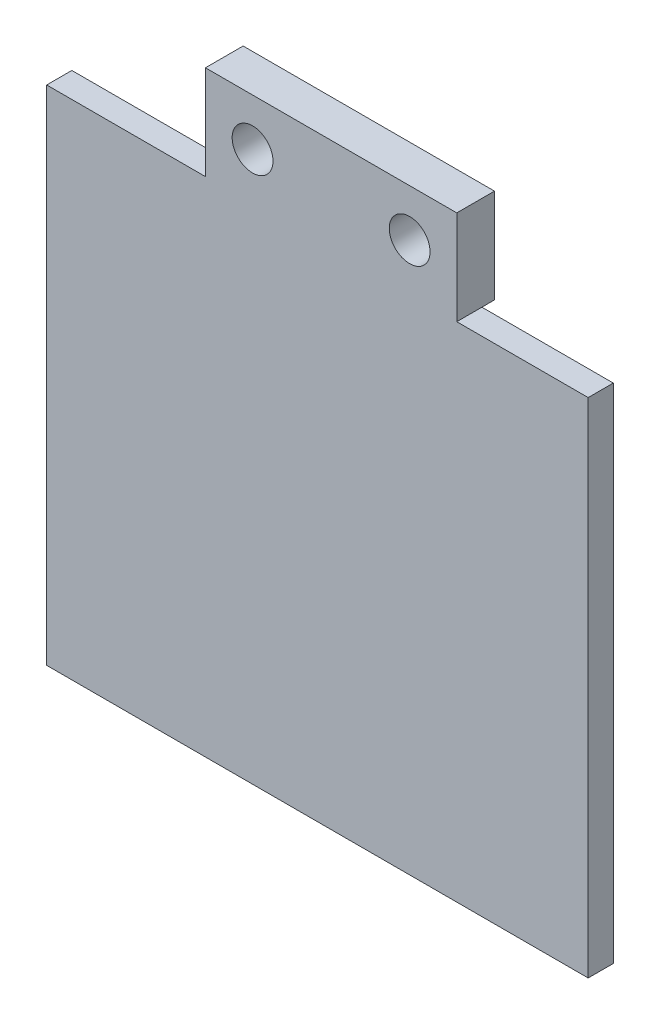
SolidWorks part; units mm, degrees
ref_plane "Front Plane" through (0, 0, 0) normal (0, 0, 1) x (1, 0, 0)
ref_plane "Top Plane" through (0, 0, 0) normal (0, 1, 0) x (1, 0, 0)
ref_plane "Right Plane" through (0, 0, 0) normal (1, 0, 0) x (0, 0, -1)
sketch "Sketch1" plane through (0, 0, 0) normal (0, 0, 1) x (1, 0, 0)
  line L0 (0, 0) -> (0, 40)
  line L1 (0, 40) -> (-7.5, 40)
  line L2 (-7.5, 40) -> (-7.5, 47.5)
  line L3 (-7.5, 47.5) -> (12.5, 47.5)
  line L4 (12.5, 47.5) -> (12.5, 40)
  line L5 (12.5, 40) -> (5, 40)
  line L6 (5, 40) -> (5, 0)
  line L7 (5, 0) -> (0, 0)
  circle A0 centre (-3.75, 43.75) radius 1.625
  circle A1 centre (8.75, 43.75) radius 1.625
  point P13 (12.5, 43.75)
  point P15 (-3.75, 40)
  point P17 (8.75, 40)
  dimension "D6" = 3.25
  dimension "D1" = 5
  dimension "D2" = 7.5
  dimension "D4" = 7.5
  dimension "D5" = 40
extrude "Boss-Extrude1" add sketch "Sketch1" along normal blind 3
sketch "Sketch2" plane through (0, 0, 3) normal (0, 0, -1) x (-1, 0, 0)
  line L1 (20.1317, 40) -> (-22.9556, 40)
  line L2 (20.1317, 40) -> (20.1317, 0)
  line L3 (20.1317, 0) -> (-22.9556, 0)
  line L4 (-22.9556, 40) -> (-22.9556, 0)
  point P4 (-28.5611, 40)
extrude "Boss-Extrude2" add sketch "Sketch2" along normal offset from surface (2 mm away) 1 up to face at (-2.125, 43.75, 0)
